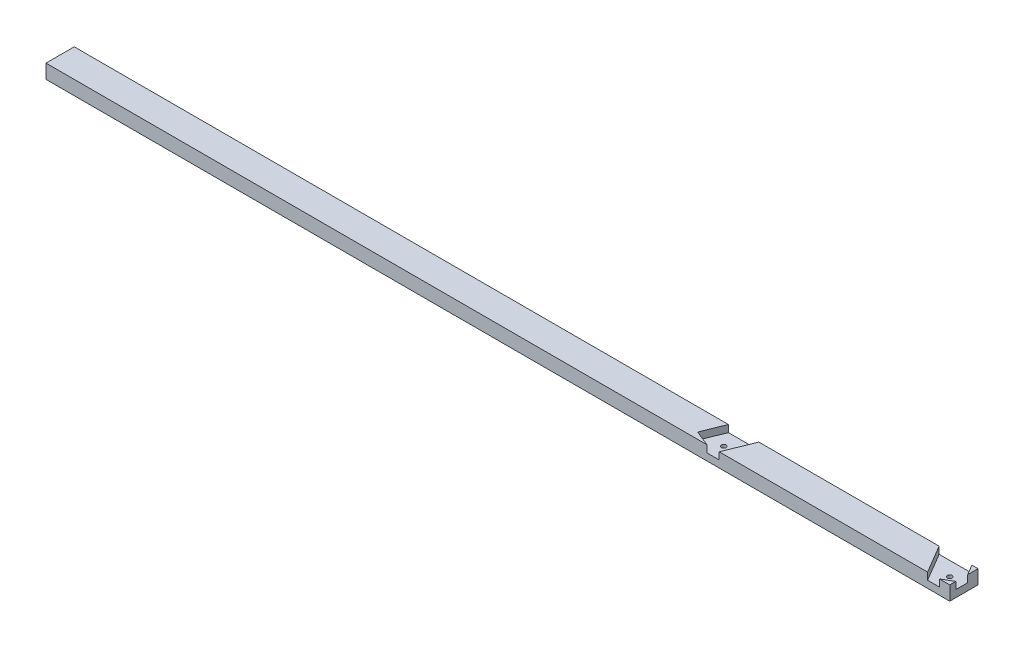
SolidWorks part; units mm, degrees
ref_plane "Front Plane" through (0, 0, 0) normal (0, 0, 1) x (1, 0, 0)
ref_plane "Top Plane" through (0, 0, 0) normal (0, 1, 0) x (1, 0, 0)
ref_plane "Right Plane" through (0, 0, 0) normal (1, 0, 0) x (0, 0, -1)
sketch "Sketch2" plane through (0, 0, 0) normal (0, 1, 0) x (1, 0, 0)
  line L0 (0, 0) -> (0, -38.1)
  line L1 (0, -38.1) -> (-1219.2, -38.1)
  line L2 (-1219.2, -38.1) -> (-1219.2, 0)
  line L3 (-1219.2, 0) -> (0, 0)
  line L4 (-323.85, -19.05) -> (-19.05, -19.05)
  line L5 (-19.05, -19.05) -> (-200.025, 287.0536)
  line L6 (-200.025, 287.0536) -> (-323.85, -19.05)
  line L7 (-323.85, -19.05) -> (-341.5098, -11.9062)
  line L8 (-323.85, -19.05) -> (-306.1902, -26.1937)
  line L9 (-341.5098, -11.9062) -> (-348.6536, -29.5661)
  line L10 (-306.1902, -26.1937) -> (-311.0065, -38.1)
  line L11 (-348.6536, -29.5661) -> (-313.3339, -43.8536)
  line L12 (108.5464, 1100.6626) -> (143.8661, 1086.3751)
  line L13 (143.8661, 1086.3751) -> (-295.5943, 0)
  line L14 (-341.5098, -11.9062) -> (108.5464, 1100.6626)
  line L15 (-200.025, 287.0536) -> (-183.6266, 296.7487)
  line L16 (-183.6266, 296.7487) -> (-193.3217, 313.1471)
  line L17 (-193.3217, 313.1471) -> (-226.1185, 293.7569)
  line L18 (-226.1185, 293.7569) -> (-52.4431, 0)
  line L19 (394.3672, -755.7411) -> (427.164, -736.3509)
  line L20 (427.164, -736.3509) -> (0, -13.8399)
  line L21 (-303.3004, -19.05) -> (-306.1902, -26.1937)
  line L22 (-8.1824, 0) -> (-183.6266, 296.7487)
  line L23 (-29.9176, -38.1) -> (394.3672, -755.7411)
  line L24 (-29.9176, -38.1) -> (-52.4431, 0)
  line L25 (0, -13.8399) -> (-8.1824, 0)
  line L26 (-303.3004, -19.05) -> (-295.5943, 0)
  line L27 (-313.3339, -43.8536) -> (-311.0065, -38.1)
  circle A0 centre (-19.05, -19.05) radius 3.175
  circle A1 centre (-323.85, -19.05) radius 3.175
  circle A2 centre (-200.025, 287.0536) radius 3.175
  point P22 (0, 730.7286)
  dimension "D5" = 6.35
  dimension "D6" = 6.35
  dimension "D18" = 6.35
  dimension "D1" = 38.1
  dimension "D2" = 1219.2
  dimension "D3" = 19.05
  dimension "D4" = 19.05
  dimension "D7" = 304.8
  dimension "D8" = 19.05
  dimension "D9" = 330.2
  dimension "D10" = 355.6
  dimension "D11" = 90
  dimension "D12" = 19.05
  dimension "D13" = 90
  dimension "D14" = 19.05
  dimension "D15" = 19.05
  dimension "D16" = 19.05
  dimension "D19" = 90
  dimension "D20" = 19.05
  dimension "D21" = 19.05
  dimension "D22" = 38.1
  dimension "D23" = 1219.2
  dimension "D24" = 38.1
  dimension "D25" = 67.976
  dimension "D26" = 295.5943
  dimension "D27" = 311.0065
  dimension "D28" = 8.1824
  dimension "D29" = 29.9176
  dimension "D30" = 52.4431
  dimension "D17" = 1219.2
extrude "Boss-Extrude2" add sketch "Sketch2" along normal blind 19.05 contours L1 L2 L3 L0
sketch "Sketch3" plane through (0, 19.05, 0) normal (0, 1, 0) x (1, 0, 0)
  line L0 (0, 0) -> (0, -38.1) construction
  line L1 (-1219.2, 0) -> (0, 0) construction
  circle A0 centre (-19.05, -19.05) radius 3.175
  circle A1 centre (-323.85, -19.05) radius 3.175
  dimension "D1" = 6.35
  dimension "D2" = 19.05
  dimension "D3" = 19.05
  dimension "D4" = 304.8
extrude "Cut-Extrude1" cut sketch "Sketch3" against normal blind 19.05
sketch "Sketch4" plane through (0, 19.05, 0) normal (0, 1, 0) x (1, 0, 0)
  line L0 (-323.85, -19.05) -> (-200.025, 287.0536)
  line L1 (-200.025, 287.0536) -> (-19.05, -19.05)
  line L2 (-306.1902, -26.1938) -> (-182.3652, 279.9098)
  line L3 (-341.5098, -11.9063) -> (-217.6848, 294.1973)
  line L4 (-341.5098, -11.9063) -> (-306.1902, -26.1938)
  line L5 (-306.1902, -26.1938) -> (-306.1211, -26.2975)
  line L6 (-348.6536, -29.5661) -> (-313.3339, -43.8536)
  line L7 (-313.3339, -43.8536) -> (-306.1902, -26.1938)
  line L8 (-348.6536, -29.5661) -> (-341.5098, -11.9063)
  line L9 (-216.4234, 277.3585) -> (-35.4484, -28.7451)
  line L10 (-183.6266, 296.7487) -> (-2.6516, -9.3549)
  line L11 (-35.4484, -28.7451) -> (-2.6516, -9.3549)
  line L12 (-25.7533, -45.1435) -> (7.0435, -25.7533)
  line L13 (-35.4484, -28.7451) -> (-25.7533, -45.1435)
  line L14 (7.0435, -25.7533) -> (-2.6516, -9.3549)
  circle M1 centre (-323.85, -19.05) radius 3.175
  circle M2 centre (-19.05, -19.05) radius 3.175
  line M3 (0, -38.1) -> (0, 0)
  line M4 (0, 0) -> (-1219.2, 0)
  line M6 (-1219.2, -38.1) -> (0, -38.1)
  dimension "D1" = 330.2
  dimension "D2" = 355.6
  dimension "D3" = 19.05
  dimension "D4" = 19.05
  dimension "D5" = 19.05
  dimension "D6" = 19.05
  dimension "D7" = 19.05
  dimension "D8" = 19.05
extrude "Cut-Extrude2" cut sketch "Sketch4" against normal blind 9.525 contours L4 L2 L0 M1 M4 | L3 L4 L0 M1 M4 | L8 L6 L7 L4 M6 M1 | L14 L11 L13 L12 M3 M2 M6 | L9 L11 L1 M2 M4 | L11 L10 L1 M2 M4 region at (-328.9223, 19.05, 7.636) region at (-309.7313, 19.05, 11.2854) region at (-328.2228, 19.05, 27.1886) region at (-35.1787, 19.05, 12.0144) region at (-14.8115, 19.05, 26.5707) region at (-16.0823, 19.05, 7.123)
